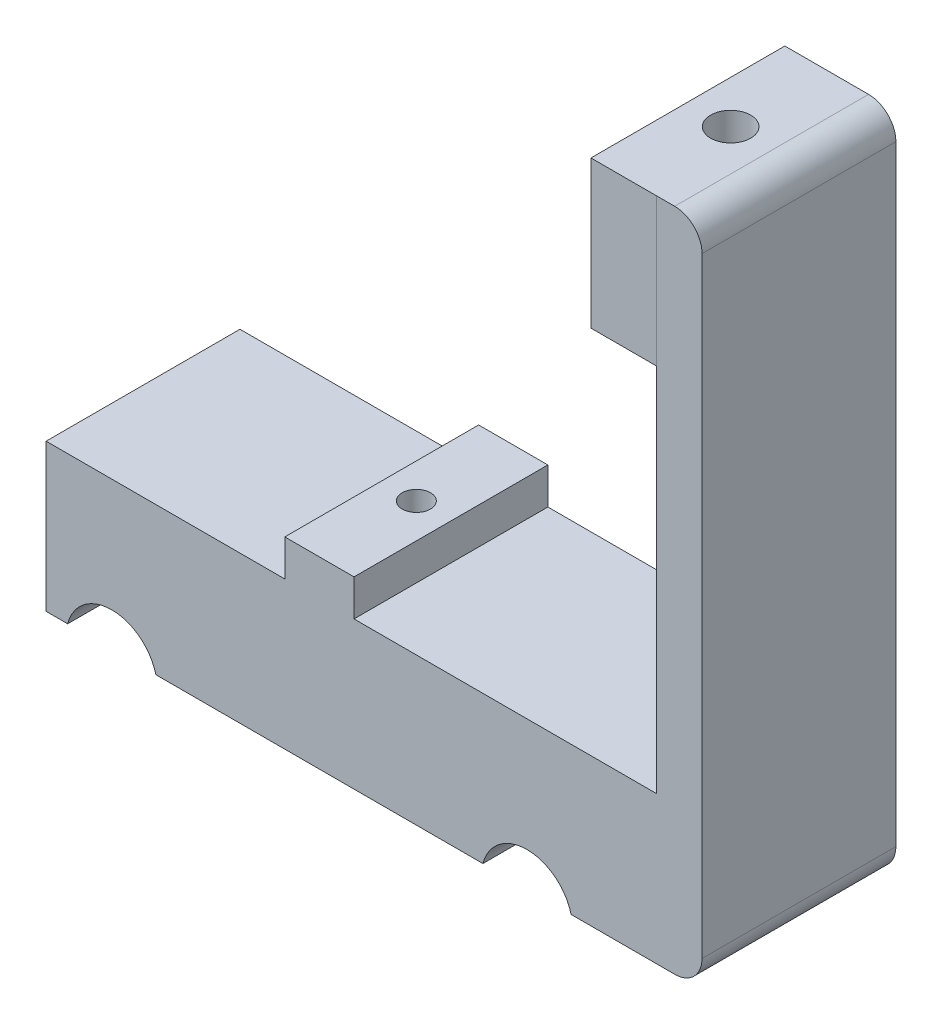
SolidWorks part; units mm, degrees
ref_plane "Front Plane" through (0, 0, 0) normal (0, 0, 1) x (1, 0, 0)
ref_plane "Top Plane" through (0, 0, 0) normal (0, 1, 0) x (1, 0, 0)
ref_plane "Right Plane" through (0, 0, 0) normal (1, 0, 0) x (0, 0, -1)
sketch "Sketch2" plane through (0, 0, 0) normal (0, 0, 1) x (1, 0, 0)
  line L0 (10.1, 0) -> (-10.1, 0)
  line L1 (-10.1, 0) -> (-10.1, 1.7099)
  line L2 (-10.1, 1.7099) -> (-6.2548, 7)
  line L3 (-6.2548, 7) -> (6.2548, 7)
  line L4 (0, 7) -> (0, 0)
  line L5 (0, 0) -> (0, 9.2516) construction
  line L6 (10.1, 1.7099) -> (6.2548, 7)
  line L7 (10.1, 0) -> (10.1, 1.7099)
  dimension "D1" = 20.2
  dimension "D2" = 7
extrude "Boss-Extrude1" add sketch "Sketch2" along normal blind 10.8 contours L4 L3 L2 L1 L0 | L0 L7 L6 L3 L4 region at (4.4168, 3.2082, 0) region at (-4.4168, 3.2082, 0)
sketch "Sketch4" plane through (0, 0, 0) normal (0, 0, 1) x (1, 0, 0)
  line L0 (-3.8, 0) -> (-3.8, -4.8)
  line L1 (10.1, 0) -> (-10.1, 0) construction
  line L2 (-3.8, -4.8) -> (-30, -4.8)
  line L3 (-30, -4.8) -> (-30, -29.8)
  line L4 (-30, -29.8) -> (30, -29.8)
  line L5 (0, 0) -> (0, -29.8) construction
  line L6 (0, -29.8) -> (0, 0)
  line L7 (3.8, 0) -> (-3.8, 0)
  line L8 (0, 0) -> (0, -30.5381) construction
  line L9 (30, -4.8) -> (30, -29.8)
  line L10 (3.8, -4.8) -> (30, -4.8)
  line L11 (3.8, 0) -> (3.8, -4.8)
  line L13 (-30, -20.98) -> (30, -20.98)
  line L14 (-30, -20.98) -> (-30, -23.48)
  line L15 (-30, -23.48) -> (30, -23.48)
  line L16 (30, -20.98) -> (30, -23.48)
  dimension "D1" = 4.8
  dimension "D2" = 3.8
  dimension "D3" = 25
  dimension "D4" = 60
  dimension "D6" = 8.82
extrude "Boss-Extrude2" add sketch "Sketch4" along normal mid plane 21.28 contours L6 L7 L0 L2 L3 L4 | L11 L7 L6 L4 L9 L10 region at (-14.5256, -12.5101, 0) region at (14.5256, -12.5101, 0)
sketch "Sketch5" plane through (0, 0, 0) normal (0, 0, 1) x (1, 0, 0)
  line L0 (-29.791, -22.2274) -> (26.9734, -22.2274) construction
  line L3 (0, -20.98) -> (0, 7) construction
  line L5 (-6.2548, 7) -> (6.2548, 7) construction
  line L20 (-30, -20.98) -> (30, -20.98) construction
  circle A0 centre (-22.791, -22.2274) radius 5
  circle A1 centre (22.791, -22.2274) radius 5
  point P2 (0, -29.8)
  point P3 (0, -22.687)
  dimension "D1" = 7
extrude "Cut-Extrude1" cut sketch "Sketch5" along normal through all both and the other way through all
fillet "Fillet1" radius 1 6 edges at (-10.1, 0, 5.4) (-10.1, 1.7099, 5.4) (-6.2548, 7, 5.4) (6.2548, 7, 5.4) (10.1, 0, 5.4) (10.1, 1.7099, 5.4)
sketch "Sketch6" plane through (30, 0, 0) normal (1, 0, 0) x (0, 0, -1)
  line L0 (-10.64, -20.98) -> (10.64, -20.98) construction
  line L1 (-10.64, -4.8) -> (10.64, -4.8)
  line L2 (-10.64, -4.8) -> (-10.64, -20.98)
  line L3 (-10.64, -20.98) -> (10.64, -20.98)
  line L4 (10.64, -4.8) -> (10.64, -20.98)
  point P6 (-10.64, -20.98)
  point P9 (-10, -4.8)
  point P10 (-10, -4.8)
  point P11 (-10.64, -4.8)
  point P15 (0, -20.98)
  point P16 (10.64, -20.98)
  point P18 (0, 0)
  point P19 (10.64, -4.8)
extrude "Boss-Extrude3" add sketch "Sketch6" along normal blind 12
sketch "Sketch7" plane through (0, -4.8, 0) normal (0, 1, 0) x (1, 0, 0)
  line L0 (3.8, -10.64) -> (42, -10.64) construction
  line L1 (42, 10.6413) -> (37, 10.6413)
  line L2 (42, 10.6413) -> (42, -10.64)
  line L3 (42, -10.64) -> (37, -10.64)
  line L4 (37, 10.6413) -> (37, -10.64)
  dimension "D1" = 5
extrude "Boss-Extrude4" add sketch "Sketch7" along normal blind 56.83
sketch "Sketch8" plane through (37, 0, 0) normal (-1, 0, 0) x (0, 0, 1)
  line L0 (-10.6413, 52.03) -> (-10.6413, -4.8) construction
  line L1 (10.643, 52.03) -> (-10.6413, 52.03)
  line L2 (10.643, 52.03) -> (10.643, 35.85)
  line L3 (10.643, 35.85) -> (-10.6413, 35.85)
  line L4 (-10.6413, 52.03) -> (-10.6413, 35.85)
  dimension "D1" = 16.18
extrude "Boss-Extrude5" add sketch "Sketch8" along normal blind 7.19
fillet "Fillet3" radius 3 2 edges at (42, 52.03, -0.0007) (42, -20.98, 0)
sketch "Sketch9" plane through (0, -20.98, 0) normal (0, -1, 0) x (1, 0, 0)
  line L0 (27.6329, 0) -> (27.6329, 10.8) construction
  line L2 (27.6329, 10.64) -> (39, 10.64) construction
  circle A0 centre (34.5029, 0) radius 2.2
  point P4 (34.5029, 4.423)
  dimension "D1" = 6.87
  dimension "D2" = 10.64
extrude "Cut-Extrude2" cut sketch "Sketch9" against normal through all
sketch "Sketch10" plane through (0, -20.98, 0) normal (0, -1, 0) x (1, 0, 0)
  line L2 (-17.9491, 0) -> (-17.9491, 10.8) construction
  line L3 (-17.9491, 10.64) -> (17.9491, 10.64) construction
  circle A0 centre (0.0009, 0) radius 1.555
  dimension "D1" = 10.64
  dimension "D2" = 17.95
extrude "Cut-Extrude3" cut sketch "Sketch10" against normal through all
sketch "Sketch11" plane through (0, 0, 10.8) normal (0, 0, 1) x (1, 0, 0)
  line L0 (9.1, 0) -> (-9.1, 0) construction
  line L1 (-12.6098, 8.9215) -> (12.3675, 8.9215)
  line L2 (-12.6098, 8.9215) -> (-12.6098, -0.8)
  line L3 (-12.6098, -0.8) -> (12.3675, -0.8)
  line L4 (12.3675, 8.9215) -> (12.3675, -0.8)
  dimension "D1" = 0.8
extrude "Cut-Extrude4" cut sketch "Sketch11" against normal through all
